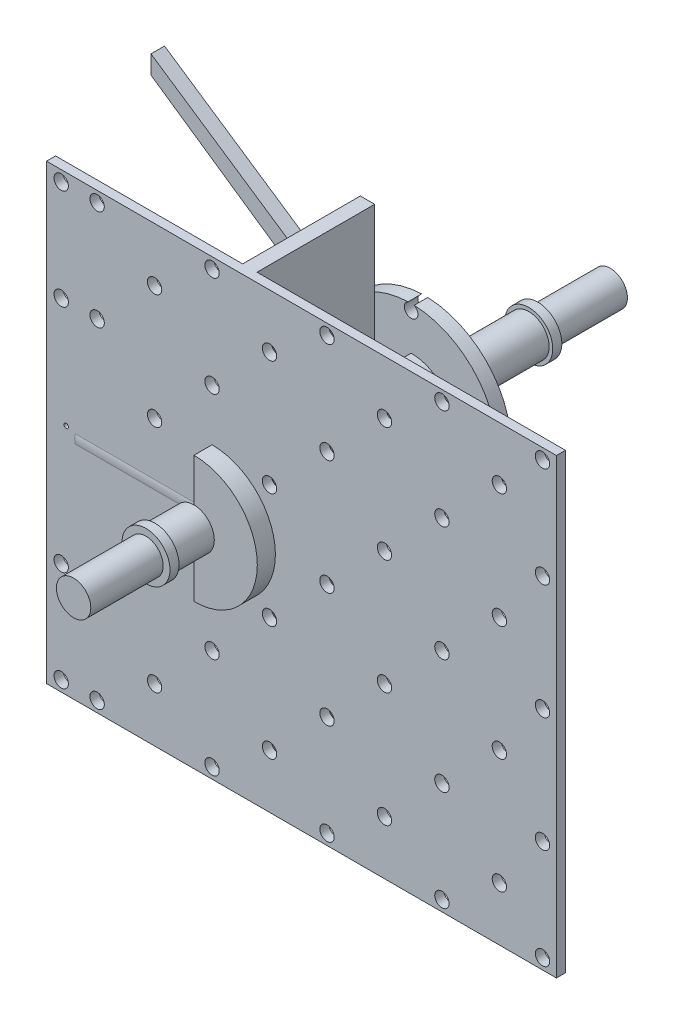
SolidWorks part; units mm, degrees
ref_plane "Front Plane" through (0, 0, 0) normal (0, 0, 1) x (1, 0, 0)
ref_plane "Top Plane" through (0, 0, 0) normal (0, 1, 0) x (1, 0, 0)
ref_plane "Right Plane" through (0, 0, 0) normal (1, 0, 0) x (0, 0, -1)
sketch "Sketch1" plane through (0, 0, 0) normal (0, 0, 1) x (1, 0, 0)
  circle A0 centre (0, 0) radius 3.8
extrude "Extrude1" add sketch "Sketch1" along normal blind 16
sketch "Sketch2" plane through (0, 0, 16) normal (0, 0, 1) x (1, 0, 0)
  circle A0 centre (0, 0) radius 4.5
extrude "Extrude2" add sketch "Sketch2" along normal blind 21
sketch "Sketch3" plane through (0, 0, 37) normal (0, 0, 1) x (1, 0, 0)
  circle A0 centre (0, 0) radius 11.1
extrude "Extrude3" add sketch "Sketch3" along normal blind 4
sketch "Sketch4" plane through (0, 0, 41) normal (0, 0, 1) x (1, 0, 0)
  circle A0 centre (0, 0) radius 6.35
  circle A1 centre (0, 0) radius 19.05
extrude "Extrude4" add sketch "Sketch4" along normal blind 3
sketch "Sketch5" plane through (0, 0, 44) normal (0, 0, 1) x (1, 0, 0)
  circle A1 centre (17.7, 0) radius 1.5
  circle A2 centre (0, -17.7) radius 1.5
  circle A3 centre (0, 17.7) radius 1.5
  circle A4 centre (-17.7, 0) radius 1.5
extrude "Extrude5" cut sketch "Sketch5" against normal up to surface (3 mm away) up to face at (19.05, 0, 41)
sketch "Sketch6" plane through (0, 0, 44) normal (0, 0, 1) x (1, 0, 0)
  line L0 (-57.5, -61.9125) -> (-57.5, 65.0875) construction
  line L1 (66.7861, -34) -> (-118.9765, -34) construction
  line L2 (-158.75, 34) -> (71.443, 34) construction
  line L3 (-12.7, -3.175) -> (-57.5, -34)
  line L4 (-12.7, 3.175) -> (-57.5, 34)
  line L5 (-57.5, 38.0733) -> (-12.7, 7.9375)
  line L6 (-12.7, 7.9375) -> (-12.7, 3.175)
  line L7 (-57.5, 34) -> (-57.5, 38.0733)
  line L8 (-57.5, -38.2889) -> (-12.7, -7.9375)
  line L9 (-12.7, -7.9375) -> (-12.7, -3.175)
  line L10 (-57.5, -38.2889) -> (-57.5, -34)
  dimension "D1" = 57.5
  dimension "D2" = 34
  dimension "D3" = 34
extrude "Extrude6" add sketch "Sketch6" against normal blind 3
sketch "Sketch9" plane through (0, 0, 44) normal (0, 0, 1) x (1, 0, 0)
  line L0 (0, -20.6375) -> (0, 4.7625) construction
  line L1 (5.7625, -20.6375) -> (5.7625, 14.2875) construction
  line L2 (0, -6.35) -> (0, -9.525)
  line L3 (5.7625, -2.6676) -> (5.7625, -7.5841)
  line L4 (5.7625, 2.6676) -> (5.7625, 7.5841)
  line L5 (0, 6.35) -> (0, 9.525)
  circle A0 centre (0, 0) radius 9.525 construction
  arc A1 (0, -6.35) -> (5.7625, -2.6676) centre (0, 0) ccw
  arc A2 (0, -9.525) -> (5.7625, -7.5841) centre (0, 0) ccw
  arc A3 (5.7625, 2.6676) -> (0, 6.35) centre (0, 0) ccw
  circle A4 centre (0, 0) radius 6.35 construction
  arc A5 (5.7625, 7.5841) -> (0, 9.525) centre (0, 0) ccw
  dimension "D1" = 19.05
  dimension "D2" = 5.7625
extrude "Extrude9" add sketch "Sketch9" along normal blind 16
sketch "Sketch10" plane through (0, 0, 60) normal (0, 0, 1) x (1, 0, 0)
  line L0 (-76.2, 50) -> (52.3875, 50) construction
  line L1 (-76.2, -50) -> (52.3875, -50) construction
  line L2 (4.7625, -8.2489) -> (4.7625, -50)
  line L3 (4.7625, -50) -> (7.9422, -50)
  line L4 (0, -52.5) -> (34.925, -52.5) construction
  line L5 (14.2875, 52.5) -> (50.8, 52.5) construction
  line L6 (4.7625, -10) -> (4.7625, -62.5) construction
  line L7 (7.9375, -10) -> (7.9375, -60) construction
  line L8 (7.9422, -50) -> (7.9375, 50)
  line L9 (0, -6.35) -> (0, -9.525) construction
  line L11 (0, -6.35) -> (0, -9.525) construction
  line L12 (0, -9.525) -> (0, -6.35)
  line L13 (0, 6.35) -> (0, 9.525)
  line L14 (7.9375, 50) -> (4.7625, 50)
  line L15 (4.7625, 50) -> (4.7625, 8.2489)
  line L16 (101.6, 13) -> (-100.0125, 13) construction
  line L17 (4.7625, -4.2001) -> (4.7625, 4.2001)
  line L19 (4.7625, 9.05) -> (4.7625, -52.5) construction
  arc A0 (0, -6.35) -> (4.7625, -4.2001) centre (0, 0) ccw
  arc A2 (0, -9.525) -> (4.7625, -8.2489) centre (0, 0) ccw
  arc A3 (0, 6.35) -> (4.7625, 4.2001) centre (0, 0) cw
  arc A4 (5.7625, 2.6676) -> (0, 6.35) centre (0, 0) ccw construction
  arc A5 (0, 6.35) -> (0, -6.35) centre (0, 0) ccw construction
  arc A6 (0, 9.525) -> (4.7625, 8.2489) centre (0, 0) cw
extrude "Extrude10" add sketch "Sketch10" along normal blind 26
sketch "Sketch11" plane through (0, 0, 86) normal (0, 0, 1) x (1, 0, 0)
  line L0 (4.7625, -50) -> (7.9422, -50)
  line L1 (4.7625, 50) -> (7.9375, 50)
  line L2 (7.9422, -50) -> (76.1014, -50)
  line L3 (76.1014, -50) -> (76.1014, 50)
  line L4 (76.1014, 50) -> (7.9375, 50)
  line L5 (4.7625, 50) -> (-36.5715, 50)
  line L6 (-36.5715, 50) -> (-36.5715, -50)
  line L8 (-36.5715, -50) -> (4.7625, -50)
  line L9 (4.7625, -42.8625) -> (4.7625, 33.3375) construction
  line L10 (4.7625, -8.2489) -> (4.7625, -50) construction
  line L11 (4.7625, 50) -> (4.7625, 8.2489) construction
  circle A0 centre (50.8, 25.4) radius 1.5875
  circle A1 centre (25.4, 25.4) radius 1.5875
  circle A2 centre (0, 25.4) radius 1.5875
  circle A3 centre (-25.4, 25.4) radius 1.5875
  circle A4 centre (-32.2375, 1.5) radius 0.5
  circle A5 centre (0, 0) radius 1.5875
  circle A6 centre (25.4, 0) radius 1.5875
  circle A7 centre (50.8, 0) radius 1.5875
  circle A8 centre (50.8, -25.4) radius 1.5875
  circle A9 centre (25.4, -25.4) radius 1.5875
  circle A10 centre (0, -25.4) radius 1.5875
  circle A11 centre (-25.4, -25.4) radius 1.5875
  circle A12 centre (63.5, -38.1) radius 1.5875
  circle A13 centre (38.1, -38.1) radius 1.5875
  circle A14 centre (73.025, -47.625) radius 1.5875
  circle A15 centre (-12.7, -38.1) radius 1.5875
  circle A16 centre (12.7, -38.1) radius 1.5875
  circle A17 centre (-33.3375, -47.625) radius 1.5875
  circle A18 centre (63.5, -12.7) radius 1.5875
  circle A19 centre (38.1, -12.7) radius 1.5875
  circle A20 centre (12.7, -12.7) radius 1.5875
  circle A21 centre (63.5, 12.7) radius 1.5875
  circle A22 centre (38.1, 12.7) radius 1.5875
  circle A23 centre (63.5, 38.1) radius 1.5875
  circle A24 centre (38.1, 38.1) radius 1.5875
  circle A25 centre (12.7, 38.1) radius 1.5875
  circle A26 centre (-12.7, 38.1) radius 1.5875
  circle A27 centre (-12.7, 12.7) radius 1.5875
  circle A28 centre (73.025, 47.625) radius 1.5875
  circle A29 centre (50.8, -47.625) radius 1.5875
  circle A30 centre (25.4, -47.625) radius 1.5875
  circle A31 centre (0, -47.625) radius 1.5875
  circle A32 centre (-25.4, -47.625) radius 1.5875
  circle A33 centre (50.8, 47.625) radius 1.5875
  circle A34 centre (25.4, 47.625) radius 1.5875
  circle A35 centre (0, 47.625) radius 1.5875
  circle A36 centre (-25.4, 47.625) radius 1.5875
  circle A37 centre (-33.3375, 47.625) radius 1.5875
  circle A38 centre (73.025, 0) radius 1.5875
  circle A39 centre (73.025, -25.4) radius 1.5875
  circle A40 centre (73.025, 25.4) radius 1.5875
  circle A41 centre (-33.3375, 25.4) radius 1.5875
  circle A43 centre (-33.3375, -25.4) radius 1.5875
  circle A44 centre (-12.7, -12.7) radius 1.5875
  circle A45 centre (12.7, 12.7) radius 1.5875
  point P117 (-32.2375, 1.5)
  dimension "D1" = 37
  dimension "D2" = 1.5
extrude "Extrude11" add sketch "Sketch11" along normal blind 2
sketch "Sketch16" plane through (0, 0, 88) normal (0, 0, 1) x (1, 0, 0)
  line L0 (0, -14) -> (0, 14)
  circle A0 centre (0, 0) radius 14 construction
  arc A1 (0, -14) -> (0, 14) centre (0, 0) ccw
extrude "Extrude15" add sketch "Sketch16" along normal blind 4 separate body
sketch "Sketch17" plane through (0, 0, 92) normal (0, 0, 1) x (1, 0, 0)
  circle A0 centre (0, 0) radius 4.5
extrude "Extrude16" add sketch "Sketch17" along normal blind 10.6
sketch "Sketch18" plane through (0, 0, 102.6) normal (0, 0, 1) x (1, 0, 0)
  circle A0 centre (0, 0) radius 3.8
extrude "Extrude17" add sketch "Sketch18" along normal blind 16
sketch "Sketch19" plane through (0, 0, 16) normal (0, 0, -1) x (-1, 0, 0)
  circle A0 centre (0, 0) radius 5.3
extrude "Extrude19" add sketch "Sketch19" against normal blind 2
sketch "Sketch20" plane through (0, 0, 102.6) normal (0, 0, 1) x (1, 0, 0)
  circle A0 centre (0, 0) radius 5.3
extrude "Extrude20" add sketch "Sketch20" against normal blind 2
sketch "Sketch21" plane through (4.7625, 0, 0) normal (-1, 0, 0) x (0, 0, 1)
  line L0 (86, 50) -> (86, -50) construction
  circle A0 centre (83.8, 0) radius 2.2
  circle A1 centre (83.8, 0) radius 4.3125
  point P0 (83.8, 0)
  point P1 (86, 0)
  dimension "D1" = 2.2
extrude "Extrude21" add sketch "Sketch21" along normal blind 35
sketch "Sketch22" plane through (4.7625, 0, 0) normal (-1, 0, 0) x (0, 0, 1)
  line L0 (86, 50) -> (86, -50) construction
  circle A0 centre (83.8, 0) radius 1.5
  point P0 (83.8, 0)
  dimension "D1" = 2.2
extrude "Extrude22" cut sketch "Sketch22" against normal blind 25
